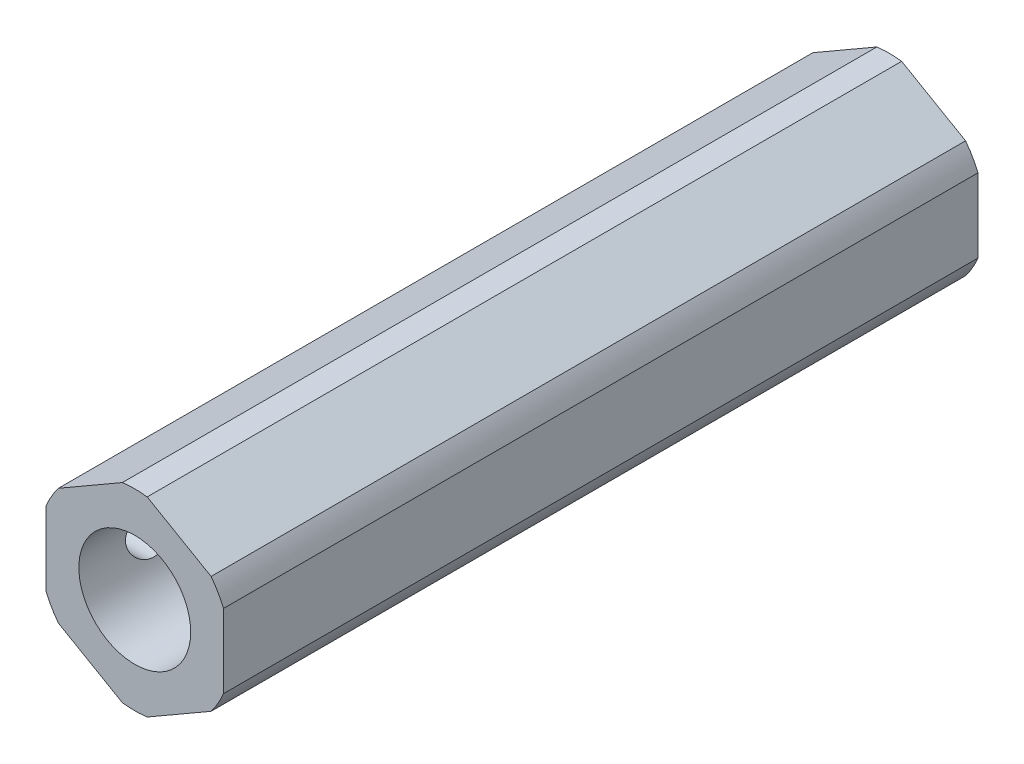
SolidWorks part; units mm, degrees
material "ThunderHex"
ref_plane "Front Plane" through (0, 0, 0) normal (0, 0, 1) x (1, 0, 0)
ref_plane "Top Plane" through (0, 0, 0) normal (0, 1, 0) x (1, 0, 0)
ref_plane "Right Plane" through (0, 0, 0) normal (1, 0, 0) x (0, 0, -1)
ref_plane "End1" through (0, 0, 26.9875) normal (0, 0, 1) x (1, 0, 0)
ref_plane "End2" through (0, 0, -26.9875) normal (0, 0, 1) x (1, 0, 0)
sketch "Sketch1" plane through (0, 0, 0) normal (0, 0, 1) x (1, 0, 0)
  circle A0 centre (0, 0) radius 6.35
  dimension "D1" = 12.7
extrude "Basic Rod" add sketch "Sketch1" along normal up to surface (26.9875 mm away) and the other way up to surface (26.9875 mm away) up to plane "End1" other way up to plane "End2"
ref_axis "Center Axis" through (0, 0, -38.2778) along (0, 0, 1)
sketch "Sketch8" plane through (0, 0, 0) normal (0, 0, 1) x (1, 0, 0)
  line L0 (-5.4616, 4.1791) -> (-6.35, 3.6662) construction
  line L1 (-0.8884, 6.8194) -> (-5.4616, 4.1791)
  line L2 (-6.35, 2.6403) -> (-6.35, -2.6403)
  line L3 (-5.4616, -4.1791) -> (-0.8884, -6.8194)
  line L4 (0.8884, -6.8194) -> (5.4616, -4.1791)
  line L5 (6.35, -2.6403) -> (6.35, 2.6403)
  line L6 (5.4616, 4.1791) -> (0.8884, 6.8194)
  line L7 (-6.35, 3.6662) -> (-6.35, 2.6403) construction
  line L8 (0, 7.3323) -> (-0.8884, 6.8194) construction
  line L9 (0.8884, 6.8194) -> (0, 7.3323) construction
  line L10 (6.35, 3.6662) -> (5.4616, 4.1791) construction
  line L11 (6.35, 2.6403) -> (6.35, 3.6662) construction
  line L12 (6.35, -3.6662) -> (6.35, -2.6403) construction
  line L13 (5.4616, -4.1791) -> (6.35, -3.6662) construction
  line L14 (0, -7.3323) -> (0.8884, -6.8194) construction
  line L15 (-0.8884, -6.8194) -> (0, -7.3323) construction
  line L16 (-6.35, -3.6662) -> (-5.4616, -4.1791) construction
  line L17 (-6.35, -2.6403) -> (-6.35, -3.6662) construction
  circle A0 centre (0, 0) radius 6.35 construction
  arc A1 (-6.35, -2.6403) -> (-5.4616, -4.1791) centre (0, 0) ccw
  circle A2 centre (0, 0) radius 6.35 construction
  arc A3 (-6.35, 2.6403) -> (-6.35, -2.6403) centre (0, 0) ccw construction
  arc A4 (-0.8884, 6.8194) -> (-5.4616, 4.1791) centre (0, 0) ccw construction
  arc A5 (-5.4616, 4.1791) -> (-6.35, 2.6403) centre (0, 0) ccw
  arc A6 (5.4616, 4.1791) -> (0.8884, 6.8194) centre (0, 0) ccw construction
  arc A7 (0.8884, 6.8194) -> (-0.8884, 6.8194) centre (0, 0) ccw
  arc A8 (6.35, -2.6403) -> (6.35, 2.6403) centre (0, 0) ccw construction
  arc A9 (6.35, 2.6403) -> (5.4616, 4.1791) centre (0, 0) ccw
  arc A10 (0.8884, -6.8194) -> (5.4616, -4.1791) centre (0, 0) ccw construction
  arc A11 (5.4616, -4.1791) -> (6.35, -2.6403) centre (0, 0) ccw
  arc A12 (-5.4616, -4.1791) -> (-0.8884, -6.8194) centre (0, 0) ccw construction
  arc A13 (-0.8884, -6.8194) -> (0.8884, -6.8194) centre (0, 0) ccw
  dimension "D1" = 13.7541
extrude "THex" add sketch "Sketch8" along normal mid plane 53.975
sketch "Sketch5" plane through (0, 0, 0) normal (0, 0, 1) x (1, 0, 0)
  line L1 (-3.6662, 6.35) -> (-7.3323, 0)
  line L2 (-7.3323, 0) -> (-3.6662, -6.35)
  line L3 (-3.6662, -6.35) -> (3.6662, -6.35)
  line L4 (3.6662, -6.35) -> (7.3323, 0)
  line L5 (7.3323, 0) -> (3.6662, 6.35)
  line L6 (3.6662, 6.35) -> (-3.6662, 6.35)
  circle A0 centre (0, 0) radius 6.35 construction
  circle A2 centre (0, 0) radius 6.35 construction
extrude "Hex" [suppressed] add sketch "Sketch5" along normal mid plane 53.975
sketch "Sketch7" plane through (0, 0, 0) normal (1, 0, 0) x (0, 0, -1)
  line L0 (0, 0) -> (-50000, 0) construction
  line L1 (-26.9875, 5.9436) -> (-28.0035, 5.9436)
  line L2 (-28.0035, 5.9436) -> (-28.0035, 6.35)
  line L3 (-28.0035, 6.35) -> (-29.0195, 6.35)
  line L4 (-29.5275, 5.842) -> (-29.5275, 0)
  line L5 (-29.5275, 0) -> (-26.9875, 0)
  line L6 (-26.9875, 0) -> (-26.9875, 5.9436)
  line L7 (-29.0195, 6.35) -> (-29.5275, 5.842)
  line L8 (38.2778, 0) -> (-38.2778, 0) construction
  line L9 (-26.9875, 5.2388) -> (-26.9875, -5.2388) construction
  point P7 (-29.5275, 6.35)
  dimension "D1" = 12.7
  dimension "D4" = 1.016
  dimension "D2" = 0.4064
  dimension "D3" = 2.54
revolve "1stSnapRing" [suppressed] add sketch "Sketch7" angle 360 about axis through (0, 0, -38.2778) along (0, 0, 1)
mirror "2ndSnapRing" [suppressed] about plane through (0, 0, 0) normal (0, 0, 1)
sketch "Sketch2" plane through (0, 0, 0) normal (0, 0, 1) x (1, 0, 0)
  circle A0 centre (0, 0) radius 2.1158
  dimension "D1" = 4.2316
extrude "Internal Cut" cut sketch "Sketch2" against normal through all both and the other way through all
sketch "Sketch9" plane through (0, 0, 26.9875) normal (0, 0, 1) x (1, 0, 0)
  circle A0 centre (0, 0) radius 4
  dimension "D1" = 8
extrude "Cut-Extrude1" cut sketch "Sketch9" against normal blind 20
sketch "Sketch10" plane through (-6.35, 0, 0) normal (-1, 0, 0) x (0, 0, 1)
  line L0 (26.9875, 0) -> (21.9862, 0) construction
  line L1 (26.9875, 2.6403) -> (26.9875, -2.6403) construction
  line L2 (21.9862, 0) -> (13.9852, 0) construction
  circle A0 centre (13.9852, 0) radius 1.6662
  circle A1 centre (21.9862, 0) radius 1.6662
  dimension "D1" = 3.3325
  dimension "D2" = 5.0013
  dimension "D3" = 8.001
extrude "Cut-Extrude2" cut sketch "Sketch10" against normal up to next
equation "\"Unit Measure\"= \"Length\"'in"
equation "\"D1@Sketch1\"=\"OD\""
equation "\"D1\"= \"Length\""
equation "\"D1@Sketch2\"=\"ID\""
equation "\"Internal Cut\"= IIF ( \"ID\" = 0 ,  suppressed  ,  unsuppressed  ) "
equation "\"D1@Hex\" = \"Length\""
equation "\"Hex\" = IIF ( \"SelectionType\" = 1 , \"suppressed\" , iif ( \"SelectionType\" = 2 , \"suppressed\" , \"unsuppressed\" ) )"
equation "\"OutsideDiameter\"= \"OD\"'in"
equation "\"ThunderHexDia\"= iif ( \"OD\" < .36 , \"OD\" * 1.1 , iif ( \"OD\" < .40 , .4035 , iif ( \"OD\" < .52 , .5415 , \"OD\" * 1.1 ) ) )"
equation "\"D1@Sketch7\"=\"Thickness\""
equation "\"SRDia\"= iif ( \"OD\" = .5 , ( \"OD\" - .468 ) / 2 , iif ( \"OD\" = .375 , ( \"OD\" - .352 ) / 2 , .050 ) )"
equation "\"D2@Sketch7\"= \"SnapRingDepth\""
equation "\"1stSnapRing\"= iif ( \"SnapRingCount\" > 0 , \"unsuppressed\" , \"suppressed\" )"
equation "\"2ndSnapRing\"= iif ( \"SnapRingCount\" = 2 , \"unsuppressed\" , \"suppressed\" )"
equation "\"D1@End1\" = \"Length\" / 2"
equation "\"D1@End2\" = \"Length\""
equation "\"D1@Sketch8\"=\"ThunderHexDia\""
equation "\"D1@THex\" = \"Length\""
equation "\"THex\"= IIF ( \"SelectionType\" = 0 ,  suppressed  , iif ( \"SelectionType\" = 2 ,  suppressed  ,  unsuppressed  )  ) "
